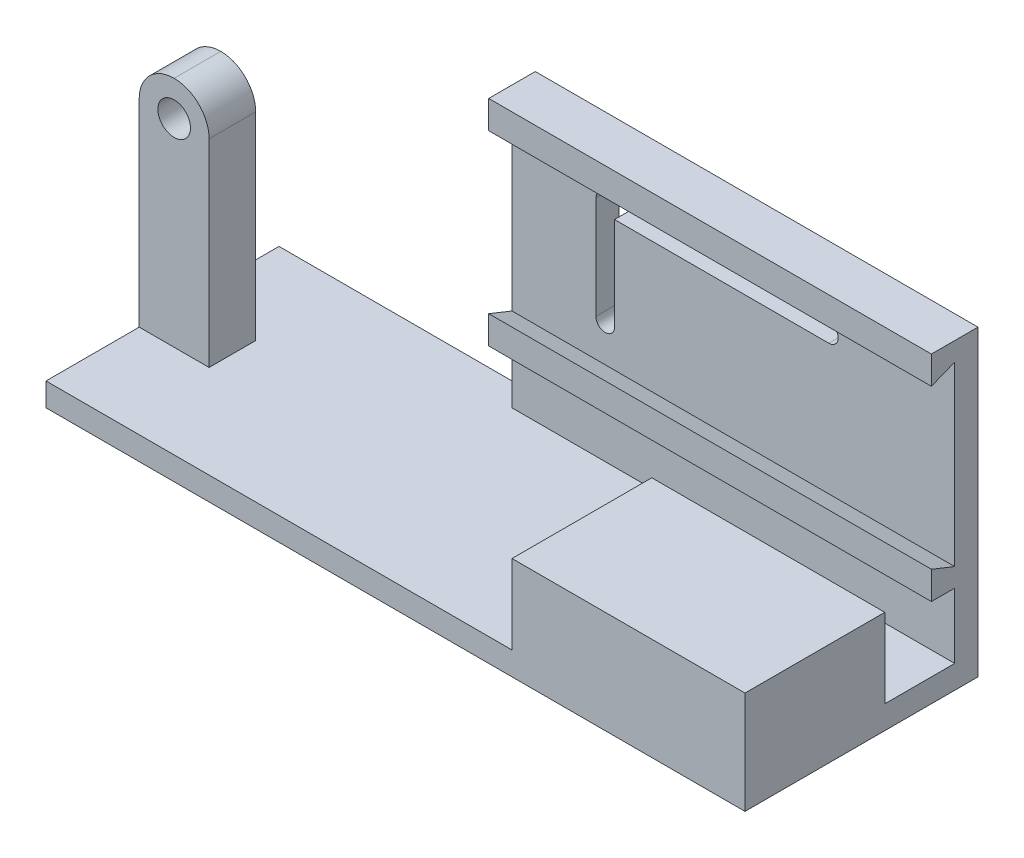
SolidWorks part; units mm, degrees
ref_plane "Front Plane" through (0, 0, 0) normal (0, 0, 1) x (1, 0, 0)
ref_plane "Top Plane" through (0, 0, 0) normal (0, 1, 0) x (1, 0, 0)
ref_plane "Right Plane" through (0, 0, 0) normal (1, 0, 0) x (0, 0, -1)
sketch "Sketch1" plane through (0, 0, 0) normal (0, 0, 1) x (1, 0, 0)
  line L1 (0, 0) -> (150, 0)
  line L2 (0, 0) -> (0, 5)
  line L3 (0, 5) -> (150, 5)
  line L4 (150, 0) -> (150, 5)
  dimension "D1" = 150
  dimension "D2" = 5
extrude "Boss-Extrude1" add sketch "Sketch1" against normal blind 50
sketch "Sketch2" plane through (0, 5, 0) normal (0, 1, 0) x (1, 0, 0)
  line L0 (0, 50) -> (0, 0) construction
  line L1 (150, 50) -> (55, 50)
  line L2 (150, 50) -> (150, 45)
  line L3 (150, 45) -> (55, 45)
  line L4 (55, 50) -> (55, 45)
  line L5 (150, 0) -> (100, 0)
  line L6 (150, 0) -> (150, 30)
  line L7 (150, 30) -> (100, 30)
  line L8 (100, 0) -> (100, 30)
  line L9 (0, 30) -> (15, 30)
  line L10 (0, 30) -> (0, 20)
  line L11 (0, 20) -> (15, 20)
  line L12 (15, 30) -> (15, 20)
  point P16 (7.5, 30)
  line M12 (0, 50) -> (0, 0)
  dimension "D1" = 5
  dimension "D2" = 95
  dimension "D3" = 50
  dimension "D4" = 30
  dimension "D5" = 15
  dimension "D6" = 10
  dimension "D7" = 15
extrude "Boss-Extrude2" add sketch "Sketch2" along normal blind 50 contours L12 L9 L11 M12
sketch "Sketch3" plane through (0, 5, 0) normal (0, 1, 0) x (1, 0, 0)
  line L1 (55, 50) -> (150, 50)
  line L2 (55, 50) -> (55, 45)
  line L3 (55, 45) -> (150, 45)
  line L4 (150, 50) -> (150, 45)
extrude "Boss-Extrude3" add sketch "Sketch3" along normal blind 60
sketch "Sketch4" plane through (0, 5, 0) normal (0, 1, 0) x (1, 0, 0)
  line L1 (100, 30) -> (150, 30)
  line L2 (100, 30) -> (100, 0)
  line L3 (100, 0) -> (150, 0)
  line L4 (150, 30) -> (150, 0)
extrude "Boss-Extrude4" add sketch "Sketch4" along normal blind 17
sketch "Sketch5" plane through (150, 0, 0) normal (1, 0, 0) x (0, 0, -1)
  line L0 (45, 65) -> (40, 65)
  line L1 (40, 65) -> (40, 59)
  line L2 (40, 59) -> (45, 61)
  line L3 (45, 65) -> (45, 5) construction
  line L4 (45, 61) -> (45, 65)
  line L5 (45, 19) -> (40, 19)
  line L6 (40, 19) -> (40, 25)
  line L7 (40, 25) -> (45, 23)
  line L8 (45, 23) -> (45, 19)
  dimension "D1" = 5
  dimension "D2" = 6
  dimension "D3" = 4
  dimension "D4" = 38
extrude "Boss-Extrude5" add sketch "Sketch5" against normal up to surface (95 mm away) up to face at (55, 35, -47.5)
fillet "Fillet1" radius 7.5 2 edges at (15, 55, -25) (0, 55, -25)
sketch "Sketch6" plane through (0, 0, -20) normal (0, 0, 1) x (1, 0, 0)
  circle A0 centre (7.5, 47.5) radius 3.5
  dimension "D1" = 7
extrude "Cut-Extrude1" cut sketch "Sketch6" against normal blind 30
sketch "Sketch7" plane through (0, 0, -45) normal (0, 0, 1) x (1, 0, 0)
  line L0 (75, 53) -> (123, 53) construction
  line L1 (75, 55) -> (123, 55)
  line L2 (75, 51) -> (123, 51)
  line L3 (55, 65) -> (150, 65) construction
  line L4 (55, 61) -> (55, 23) construction
  arc A0 (75, 55) -> (75, 51) centre (75, 53) ccw
  arc A1 (123, 51) -> (123, 55) centre (123, 53) ccw
  point P2 (99, 53)
  dimension "D1" = 2
  dimension "D2" = 12
  dimension "D3" = 20
  dimension "D4" = 48
extrude "Cut-Extrude2" cut sketch "Sketch7" against normal blind 10
sketch "Sketch8" plane through (0, 0, -45) normal (0, 0, 1) x (1, 0, 0)
  line L0 (75, 53) -> (75, 31) construction
  line L1 (77, 53) -> (77, 31)
  line L2 (73, 53) -> (73, 31)
  arc A0 (77, 53) -> (73, 53) centre (75, 53) ccw
  arc A1 (73, 31) -> (77, 31) centre (75, 31) ccw
  point P3 (75, 42)
  dimension "D1" = 2
  dimension "D2" = 22
extrude "Cut-Extrude3" cut sketch "Sketch8" against normal blind 10
sketch "Sketch10" plane through (0, 0, -50) normal (0, 0, 1) x (1, 0, 0)
  line B0 (120, 53) -> (77, 53)
  line B1 (75, 51) -> (75, 31)
  arc B2 (75, 51) -> (77, 53) centre (77, 51) cw
sketch_block_instance "Block1-1"
sketch_block "Block1" parameters "D1"=2, "D2"=18
scale "Scale1" bodies to scale 108 scale about centroid uniform scaling yes scale factor 2
scale "Scale2" bodies to scale 109 scale about centroid uniform scaling yes scale factor 1
scale "Scale3" bodies to scale 110 scale about centroid uniform scaling yes scale factor 1
scale "Scale4" bodies to scale 111 scale about centroid uniform scaling yes scale factor 0.5
